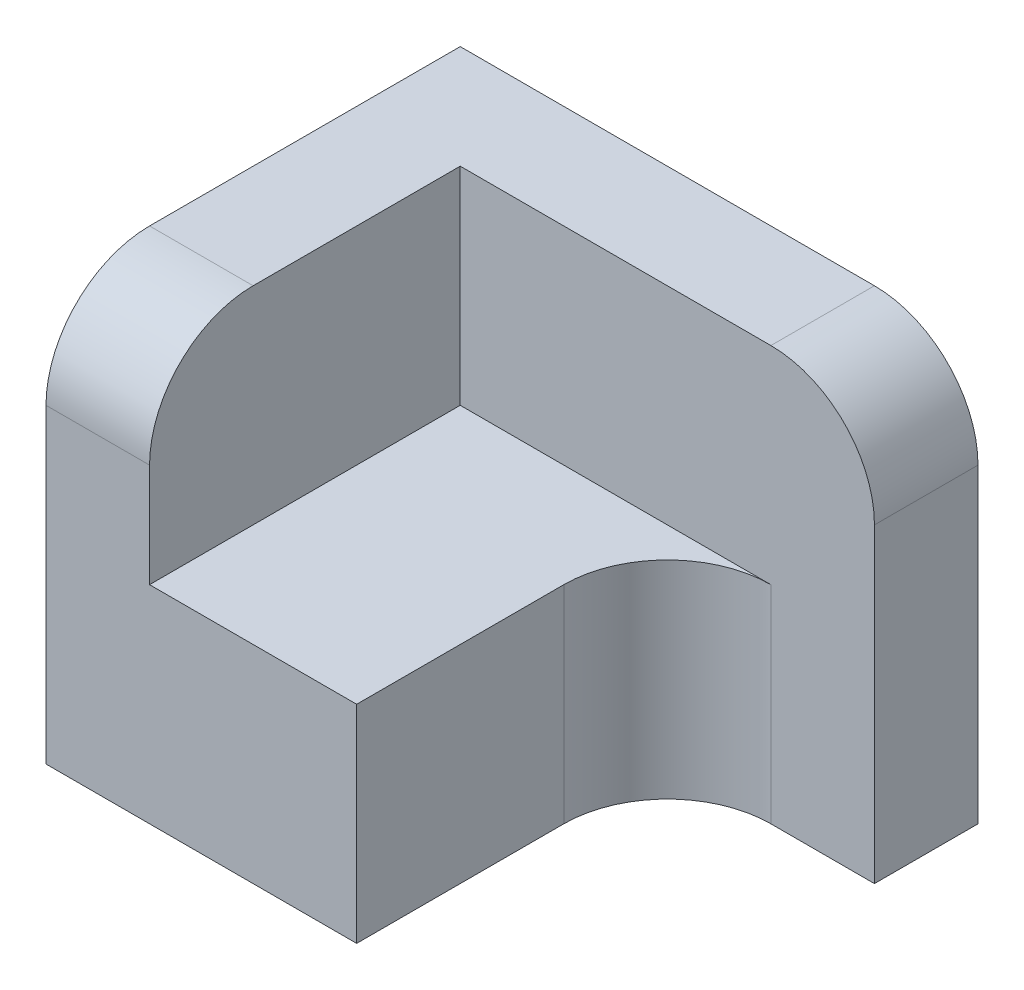
SolidWorks part; units mm, degrees
ref_plane "前基準面" through (0, 0, 0) normal (0, 0, 1) x (1, 0, 0)
ref_plane "上基準面" through (0, 0, 0) normal (0, 1, 0) x (1, 0, 0)
ref_plane "右基準面" through (0, 0, 0) normal (1, 0, 0) x (0, 0, -1)
sketch "草圖1" plane through (0, 0, 0) normal (0, 1, 0) x (1, 0, 0)
  line L1 (0, 0) -> (25, 0)
  line L2 (0, 0) -> (0, -20)
  line L3 (0, -20) -> (25, -20)
  line L4 (25, 0) -> (25, -20)
  dimension "D1" = 25
  dimension "D2" = 20
extrude "填料-伸長1" add sketch "草圖1" along normal blind 10
sketch "草圖2" plane through (0, 10, 0) normal (0, 1, 0) x (1, 0, 0)
  line L0 (25, 0) -> (0, 0) construction
  line L1 (0, -20) -> (5, -20)
  line L2 (0, 0) -> (25, 0)
  line L3 (0, -20) -> (0, 0)
  line L4 (5, -20) -> (5, -5)
  line L5 (25, -20) -> (25, 0) construction
  line L6 (0, 0) -> (-0.0011, 0.0066)
  line L7 (25, 0) -> (25, -5)
  line L8 (25, -5) -> (5, -5)
  line M3 (0, 0) -> (0, -20)
  line M4 (0, -20) -> (25, -20)
  line M5 (25, -20) -> (25, 0)
  line M6 (25, 0) -> (0, 0)
  dimension "D1" = 5
  dimension "D2" = 5
extrude "填料-伸長2" add sketch "草圖2" along normal blind 10 contours L8 L4 M5 M6 M3 M4 region at (0.3202, 10, 10)
sketch "草圖3" plane through (0, 0, 20) normal (0, 0, 1) x (1, 0, 0)
  line L0 (0, 0) -> (25, 0) construction
  line L1 (25, 10) -> (15, 10)
  line L2 (25, 10) -> (25, 0)
  line L3 (25, 0) -> (15, 0)
  line L4 (15, 10) -> (15, 0)
  dimension "D1" = 10
extrude "除料-伸長1" cut sketch "草圖3" against normal up to surface (15 mm away) up to face at (15, 15, 5)
fillet "圓角1" radius 5 3 edges at (15, 5, 5) (2.5, 20, 20) (25, 20, 2.5)
